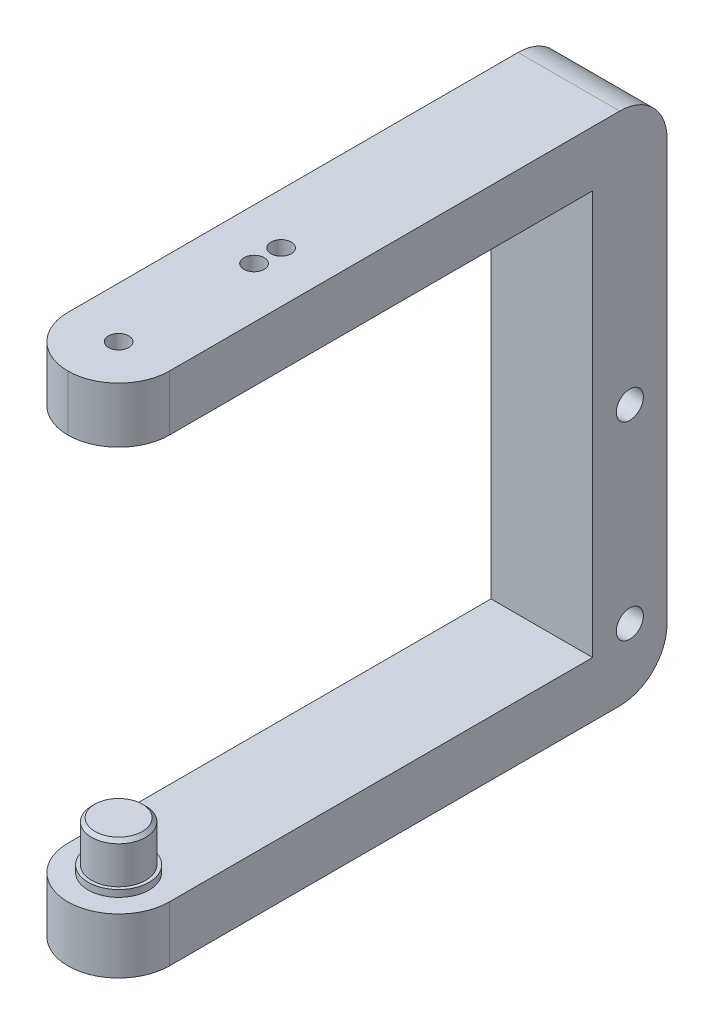
SolidWorks part; units mm, degrees
ref_plane "Piano frontale" through (0, 0, 0) normal (0, 0, 1) x (1, 0, 0)
ref_plane "Piano superiore" through (0, 0, 0) normal (0, 1, 0) x (1, 0, 0)
ref_plane "Piano destro" through (0, 0, 0) normal (1, 0, 0) x (0, 0, -1)
sketch "Schizzo1" plane through (0, 0, 0) normal (0, 0, 1) x (1, 0, 0)
  line L0 (0, 0) -> (15, 0)
  line L1 (15, 0) -> (15, 76.1)
  line L2 (15, 76.1) -> (0, 76.1)
  line L3 (0, 76.1) -> (0, 0)
  dimension "D1" = 15
  dimension "D2" = 76.1
extrude "Estrusione-Estrusione1" add sketch "Schizzo1" along normal blind 11
sketch "Schizzo2" plane through (0, 0, 11) normal (0, 0, 1) x (1, 0, 0)
  line L0 (15, 0) -> (15, 8.2)
  line L1 (15, 0) -> (15, 76.1) construction
  line L2 (15, 8.2) -> (0, 8.2)
  line L3 (0, 76.1) -> (0, 0) construction
  line L4 (0, 8.2) -> (0, 0)
  line L5 (0, 0) -> (15, 0)
  dimension "D1" = 8.2
extrude "Estrusione-Estrusione2" add sketch "Schizzo2" along normal blind 62.5
sketch "Schizzo3" plane through (0, 8.2, 0) normal (0, 1, 0) x (1, 0, 0)
  line L0 (15, -73.5) -> (0, -73.5) construction
  circle A0 centre (7.5, -73.5) radius 7.5
extrude "Estrusione-Estrusione3" add sketch "Schizzo3" against normal blind 8.2
sketch "Schizzo4" plane through (0, 8.2, 0) normal (0, 1, 0) x (1, 0, 0)
  circle A0 centre (7.5, -73.5) radius 4
extrude "Estrusione-Estrusione4" add sketch "Schizzo4" along normal blind 7
chamfer "Smusso1" distance 0.5 angle 45 1 edges at (7.5, 15.2, 77.5)
sketch "Schizzo5" plane through (0, 0, 11) normal (0, 0, 1) x (1, 0, 0)
  line L0 (15, 76.1) -> (15, 67.9)
  line L1 (15, 8.2) -> (15, 76.1) construction
  line L2 (15, 67.9) -> (0, 67.9)
  line L3 (0, 76.1) -> (0, 8.2) construction
  line L4 (0, 67.9) -> (0, 76.1)
  line L5 (0, 76.1) -> (15, 76.1)
  dimension "D1" = 8.2
extrude "Estrusione-Estrusione5" add sketch "Schizzo5" along normal blind 70
hole_wizard "Ø3.0 (3) Diameter Hole1" positions "Schizzo6" profile "Schizzo8" hole size "Ø3.0" standard "ISO"
sketch "Schizzo6" plane through (0, 76.1, 0) normal (0, 1, 0) x (1, 0, 0)
  line L1 (15, -81) -> (15, 0) construction
  line L2 (0, -81) -> (0, 0) construction
  circle A1 centre (7.5, -73.5) radius 3.5 construction
  point P0 (7.5, -49.5)
  point P2 (7.5, -53.5)
  dimension "D1" = 4
  dimension "D2" = 20
  dimension "D3" = 7.5
  dimension "D4" = 7.5
sketch "Schizzo8" plane through (7.5, 76.1, 49.5) normal (1, 0, 0) x (0, 0, 1)
  line L0 (0, 0) -> (0, 10.9013)
  line L1 (0, 10.9013) -> (1.5, 10)
  line L2 (1.5, 10) -> (1.5, 0)
  line L5 (1.5, 0) -> (0, 0)
  line L10 (0, 10.9013) -> (-1.5, 10) construction
  line L11 (0, -6.35) -> (0, 107.95) construction
  dimension "Hole Dia." = 3
  dimension "Hole Depth" = 10
  dimension "Drill Angle" = 118
fillet "Raccordo1" radius 7.5 2 edges at (15, 72, 81) (0, 72, 81)
fillet "Raccordo2" radius 7 2 edges at (7.5, 0, 0) (7.5, 76.1, 0)
hole_wizard "Ø4.0 (4) Diameter Hole1" positions "Schizzo10" profile "Schizzo11" hole size "Ø4.0" standard "ISO" end condition through all
sketch "Schizzo10" plane through (15, 0, 0) normal (1, 0, 0) x (0, 0, -1)
  line L0 (-73.5, 0) -> (-7, 0) construction
  line L1 (0, 7) -> (0, 69.1) construction
  point P0 (-5.5, 9.8)
  point P7 (-5.5, 37.8)
  dimension "D1" = 9.8
  dimension "D2" = 5.5
  dimension "D3" = 5.5
  dimension "D4" = 28
sketch "Schizzo11" plane through (15, 9.8, 5.5) normal (0, 1, 0) x (0, 0, -1)
  line L0 (0, 0) -> (0, 15)
  line L1 (0, 15) -> (2, 15)
  line L2 (2, 15) -> (2, 0)
  line L5 (2, 0) -> (0, 0)
  line L11 (0, -6.35) -> (0, 107.95) construction
  dimension "Thru Hole Dia." = 4
  dimension "Thru Hole Depth" = 15
sketch "Schizzo12" plane through (0, 8.2, 0) normal (0, 1, 0) x (1, 0, 0)
  circle A0 centre (7.5, -73.5) radius 4.5
extrude "Estrusione-Estrusione6" add sketch "Schizzo12" along normal blind 1
hole_wizard "Ø3.0 (3) Diameter Hole2" positions "Sketch1" profile "Sketch2" hole size "Ø3.0" standard "ISO" end condition up to next
sketch "Sketch1" plane through (0, 76.1, 0) normal (0, 1, 0) x (1, 0, 0)
  point P0 (7.5, -73.5)
sketch "Sketch2" plane through (7.5, 76.1, 73.5) normal (1, 0, 0) x (0, 0, 1)
  line L0 (0, 0) -> (0, 8.2)
  line L1 (0, 8.2) -> (1.5, 8.2)
  line L2 (1.5, 8.2) -> (1.5, 0)
  line L5 (1.5, 0) -> (0, 0)
  line L11 (0, -6.35) -> (0, 107.95) construction
  dimension "Thru Hole Dia." = 3
  dimension "Thru Hole Depth" = 8.2
